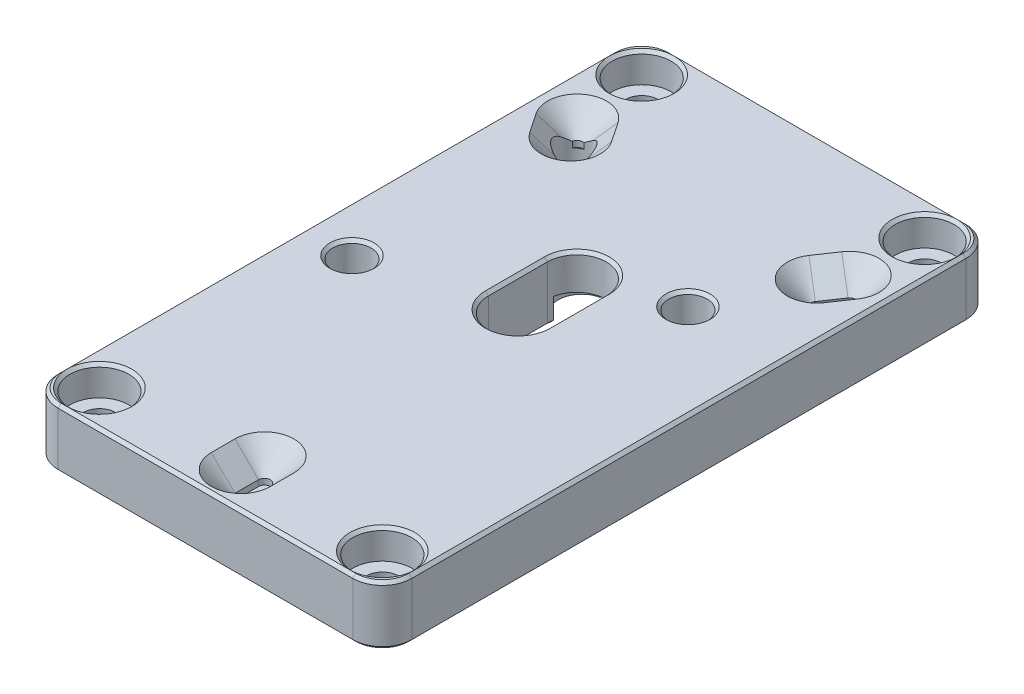
SolidWorks part; units mm, degrees
ref_plane "Front Plane" through (0, 0, 0) normal (0, 0, 1) x (1, 0, 0)
ref_plane "Top Plane" through (0, 0, 0) normal (0, 1, 0) x (1, 0, 0)
ref_plane "Right Plane" through (0, 0, 0) normal (1, 0, 0) x (0, 0, -1)
sketch "Sketch1" plane through (0, 0, 0) normal (0, 1, 0) x (1, 0, 0)
  line L1 (-30, 52) -> (30, 52)
  line L2 (-30, 52) -> (-30, -52)
  line L3 (-30, -52) -> (30, -52)
  line L4 (30, 52) -> (30, -52)
  line L5 (-30, 52) -> (30, -52) construction
  line L6 (-30, -52) -> (30, 52) construction
  point P0 (0, 0)
  dimension "D1" = 60
  dimension "D2" = 104
extrude "Boss-Extrude1" add sketch "Sketch1" along normal blind 10
sketch "Sketch10" plane through (0, 10, 0) normal (0, 1, 0) x (1, 0, 0)
  circle A0 centre (0, -44) radius 2.75 construction
  circle A1 centre (-22, 32.5) radius 2.75 construction
  circle A2 centre (22, 32.5) radius 2.75 construction
  circle A3 centre (0, -44) radius 2.75
  circle A4 centre (-22, 32.5) radius 2.75
  circle A5 centre (22, 32.5) radius 2.75
  circle A6 centre (0, 34) radius 15 construction
  circle A7 centre (0, -21.5) radius 15 construction
  circle A8 centre (0, 34) radius 15
  circle A9 centre (0, -21.5) radius 15
  circle A10 centre (0, 11) radius 1.85 construction
  circle A11 centre (0, 1) radius 1.85 construction
  circle A12 centre (0, 11) radius 1.85
  circle A13 centre (0, 1) radius 1.85
sketch "Sketch3" plane through (0, 10, 0) normal (0, 1, 0) x (1, 0, 0)
  line L0 (0, 0) -> (22, 32.5) construction
  line L1 (0, 0) -> (-22, 32.5) construction
  line L5 (0, 0) -> (0, -44) construction
  line L6 (-23.1211, 34.1562) -> (-20.8789, 30.8438) construction
  line L7 (-22.293, 34.7168) -> (-20.0508, 31.4043)
  line L8 (-23.9492, 33.5957) -> (-21.707, 30.2832)
  line L9 (23.1211, 34.1562) -> (20.8789, 30.8438) construction
  line L10 (23.9492, 33.5957) -> (21.707, 30.2832)
  line L11 (22.293, 34.7168) -> (20.0508, 31.4043)
  line L12 (0, -46) -> (0, -42) construction
  line L13 (-1, -46) -> (-1, -42)
  line L14 (1, -46) -> (1, -42)
  arc A0 (-22.293, 34.7168) -> (-23.9492, 33.5957) centre (-23.1211, 34.1562) ccw
  arc A1 (-21.707, 30.2832) -> (-20.0508, 31.4043) centre (-20.8789, 30.8438) ccw
  arc A2 (23.9492, 33.5957) -> (22.293, 34.7168) centre (23.1211, 34.1562) ccw
  arc A3 (20.0508, 31.4043) -> (21.707, 30.2832) centre (20.8789, 30.8438) ccw
  arc A4 (-1, -46) -> (1, -46) centre (0, -46) ccw
  arc A5 (1, -42) -> (-1, -42) centre (0, -42) ccw
  point P19 (-22, 32.5)
  point P25 (22, 32.5)
  point P32 (0, -44)
  dimension "D2" = 1
  dimension "D1" = 4
extrude "Cut-Extrude1" cut sketch "Sketch3" against normal blind 5
chamfer "Chamfer1" distance 4 angle 45 12 edges at (-22.8281, 10, -31.9394) (-20.3183, 10, -30.0157) (-23.6817, 10, -34.9843) (-21.1719, 10, -33.0606) (-1, 10, 44) (0, 10, 47) (0, 10, 41) (1, 10, 44) (21.1719, 10, -33.0606) (20.3183, 10, -30.0157) (23.6817, 10, -34.9843) (22.8281, 10, -31.9394)
sketch "Sketch5" plane through (0, 10, 0) normal (0, 1, 0) x (1, 0, 0)
  circle A2 centre (0, -21.5) radius 15 construction
  circle A3 centre (0, -21.5) radius 15
  circle A4 centre (0, 34) radius 15 construction
  circle A5 centre (0, 34) radius 15
extrude "Cut-Extrude3" cut sketch "Sketch5" against normal through all from offset 1.5 offset against normal yes
sketch "Sketch6" plane through (0, 10, 0) normal (0, 1, 0) x (1, 0, 0)
  line L8 (24, -46) -> (24, 46)
  line L9 (24, 46) -> (-24, 46)
  line L10 (-24, 46) -> (-24, -46)
  line L11 (-24, -46) -> (24, -46)
  line L12 (24, -46) -> (24, 46) construction
  line L13 (24, 46) -> (-24, 46) construction
  line L14 (-24, 46) -> (-24, -46) construction
  line L15 (-24, -46) -> (24, -46) construction
  dimension "D1" = 6
hole_wizard "CBORE for M5 SHCS1" positions "Sketch7" profile "Sketch8" counterbore size "M5" standard "ANSI Metric" end condition through all
sketch "Sketch7" plane through (0, 10, 0) normal (0, 1, 0) x (1, 0, 0)
  point P0 (-24, 46)
  point P3 (24, 46)
  point P6 (24, -46)
  point P9 (-24, -46)
sketch "Sketch8" plane through (-24, 10, -46) normal (1, 0, 0) x (0, 0, 1)
  line L0 (0, 0) -> (0, 10)
  line L1 (0, 10) -> (2.75, 10)
  line L3 (2.75, 10) -> (2.75, 5)
  line L4 (2.75, 5) -> (5, 5)
  line L5 (5, 5) -> (5, 0)
  line L7 (5, 0) -> (0, 0)
  line L11 (0, -6.35) -> (0, 107.95) construction
  dimension "Thru Hole Dia." = 5.5
  dimension "Thru Hole Depth" = 10
  dimension "C'Bore Dia." = 10
  dimension "C'Bore Depth" = 5
fillet "Fillet1" radius 5 4 edges at (30, 5, -52) (30, 5, 52) (-30, 5, 52) (-30, 5, -52)
sketch "Sketch9" plane through (0, 0, 0) normal (0, -1, 0) x (1, 0, 0)
  circle A0 centre (0, -19) radius 0.35
  circle A4 centre (0, -34) radius 15 construction
  dimension "D1" = 0.7
extrude "Boss-Extrude2" add sketch "Sketch9" against normal up to next
sketch "Sketch11" plane through (0, 0, 0) normal (0, -1, 0) x (1, 0, 0)
  circle A0 centre (0, 6.5) radius 0.35
  circle A1 centre (0, 21.5) radius 15 construction
  arc A2 (-0.35, -19.0041) -> (0.35, -19.0041) centre (0, -19) ccw construction
extrude "Boss-Extrude3" add sketch "Sketch11" against normal up to next contours A0
pattern_circular "CirPattern1" count 6 over 360 about axis through (0, 0, 21.5) along (0, 1, 0) of "Boss-Extrude3" reverse direction yes
pattern_circular "CirPattern2" count 6 over 360 about axis through (0, 0, -34) along (0, 1, 0) of "Boss-Extrude2" reverse direction yes
sketch "Sketch12" plane through (0, 10, 0) normal (0, 1, 0) x (1, 0, 0)
  line L0 (0, 1) -> (0, 11) construction
  line L1 (-5, 1) -> (-5, 11)
  line L2 (5, 1) -> (5, 11)
  arc A0 (-5, 1) -> (5, 1) centre (0, 1) ccw
  arc A1 (5, 11) -> (-5, 11) centre (0, 11) ccw
  point P4 (0, 6)
  dimension "D1" = 5
extrude "Cut-Extrude4" cut sketch "Sketch12" against normal through all
sketch "Sketch13" plane through (0, 0, 0) normal (0, -1, 0) x (1, 0, 0)
  line L0 (-29.5747, -105) -> (25.4932, -105) construction
  line L1 (25, -52) -> (-25, -52) construction
  line L2 (-25, -39.849) -> (17, -39.849) construction
  line L3 (-25, -39.849) -> (-25, 8.151) construction
  line L4 (-25, 8.151) -> (17, 8.151) construction
  line L5 (17, 8.151) -> (17, -39.849) construction
  line L6 (-25, 8.151) -> (17, -39.849) construction
  line L7 (14, -15.849) -> (-4, -15.849) construction
  line L8 (11.2484, 0.151) -> (11.2484, -31.849) construction
  point P6 (-22, -36.849)
  point P7 (-22, 5.151)
  point P10 (-4, -15.849)
  point P14 (14, -15.849)
  point P19 (11.2484, -15.849)
  dimension "D1" = 53
  dimension "D2" = 65.151
  dimension "D3" = 3
  dimension "D4" = 3
  dimension "D5" = 3
  dimension "D6" = 48
  dimension "D7" = 42
  dimension "D8" = 4
  dimension "D9" = 3
  dimension "D10" = 32
  dimension "D11" = 5.7516
sketch "Sketch14" plane through (0, 0, 0) normal (0, -1, 0) x (1, 0, 0)
  circle A0 centre (-4, -15.849) radius 4
  dimension "D1" = 8
extrude "Cut-Extrude5" cut sketch "Sketch14" against normal blind 4
sketch "Sketch15" plane through (0, 0, -52) normal (0, 0, -1) x (-1, 0, 0)
  line L0 (-25, 0) -> (25, 0) construction
  line L1 (0, 0) -> (0, -6) construction
  line L2 (8, 0) -> (-8, 0)
  arc A0 (8, 0) -> (-8, 0) centre (0, -6) ccw
  dimension "D1" = 10
  dimension "D2" = 6
extrude "Cut-Extrude6" cut sketch "Sketch15" against normal up to next
hole_wizard "CBORE for M3 SHCS1" positions "Sketch17" profile "Sketch18" counterbore size "M3" standard "ANSI Metric" end condition through all
sketch "Sketch17" plane through (0, 10, 0) normal (0, 1, 0) x (1, 0, 0)
  point P1 (-22, -5.151)
  point P5 (14, 15.849)
  point P13 (0, 0)
sketch "Sketch18" plane through (-22, 10, 5.151) normal (1, 0, 0) x (0, 0, 1)
  line L0 (0, 0) -> (0, 10)
  line L1 (0, 10) -> (1.7, 10)
  line L3 (1.7, 10) -> (1.7, 7)
  line L4 (1.7, 7) -> (3.25, 7)
  line L5 (3.25, 7) -> (3.25, 0)
  line L7 (3.25, 0) -> (0, 0)
  line L11 (0, -6.35) -> (0, 107.95) construction
  dimension "Thru Hole Dia." = 3.4
  dimension "Thru Hole Depth" = 10
  dimension "C'Bore Dia." = 6.5
  dimension "C'Bore Depth" = 7
chamfer "Chamfer2" distance 0.5 angle 45 32 edges at (0, 0, 52) (28.5355, 0, 50.5355) (-28.5355, 0, 50.5355) (30, 0, 0) (-30, 0, 0) (28.5355, 0, -50.5355) (-28.5355, 0, -50.5355) (16.5, 0, -52) (-16.5, 0, -52) (-5, 0, -6) (0, 0, 4) (-4.977, 0, -11.4789) (3.5345, 0, -14.5365) (5, 0, -6) (24, 10, 51) (-24, 10, 51) (-24, 10, -41) (24, 10, -41) (-5, 10, -6) (0, 10, 4) (0, 10, -16) (5, 10, -6) (-30, 10, 0) (-28.5355, 10, 50.5355) (-28.5355, 10, -50.5355) (0, 10, 52) (0, 10, -52) (28.5355, 10, 50.5355) (28.5355, 10, -50.5355) (30, 10, 0) (-22, 10, 8.401) (14, 10, -12.599)
sketch "Sketch19" plane through (0, 10, 0) normal (0, 1, 0) x (1, 0, 0)
  circle A0 centre (-22, 32.5) radius 2.8
  dimension "D1" = 5.6
extrude "Cut-Extrude8" cut sketch "Sketch19" against normal up to surface (7 mm away) contours A0 up to face at (14, 3, -14.149)
sketch "Sketch20" plane through (0, 3, 0) normal (0, 1, 0) x (1, 0, 0)
  circle A0 centre (-22, 32.5) radius 1.6
  circle A1 centre (-22, 32.5) radius 2.8 construction
  dimension "D1" = 3.2
extrude "Cut-Extrude9" cut sketch "Sketch20" against normal through all
